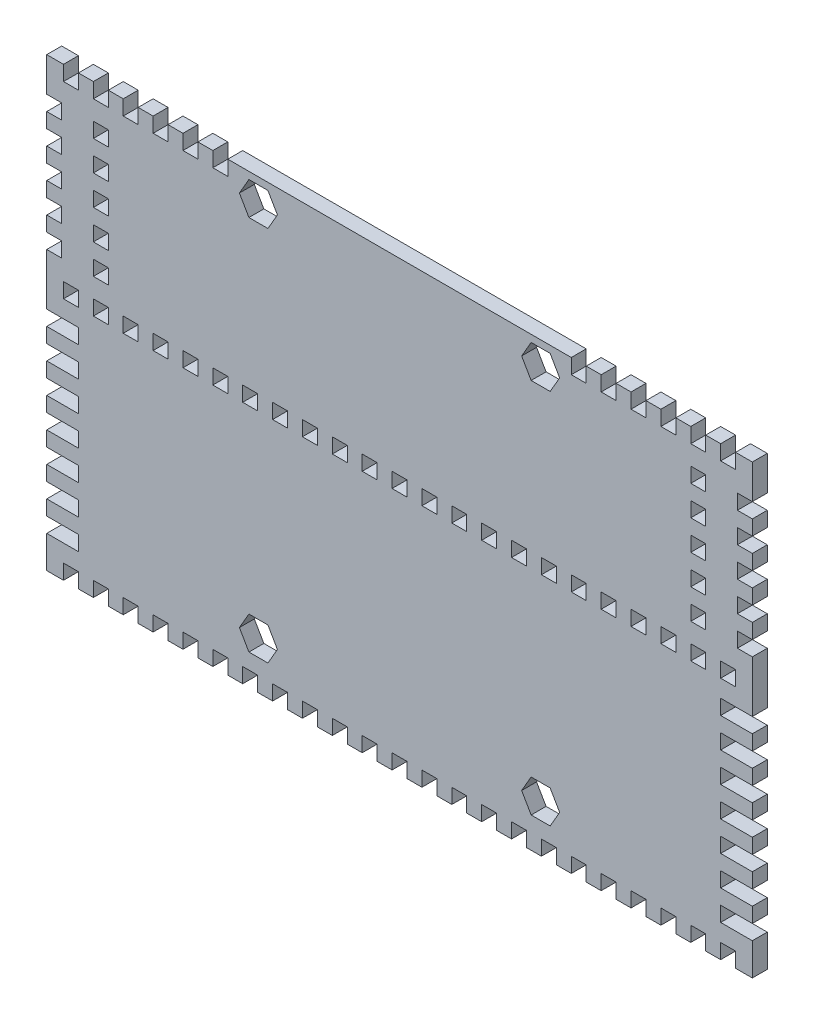
SolidWorks part; units mm, degrees
ref_plane "Front Plane" through (0, 0, 0) normal (0, 0, 1) x (1, 0, 0)
ref_plane "Top Plane" through (0, 0, 0) normal (0, 1, 0) x (1, 0, 0)
ref_plane "Right Plane" through (0, 0, 0) normal (1, 0, 0) x (0, 0, -1)
sketch "Sketch1" plane through (0, 0, 0) normal (0, 0, 1) x (1, 0, 0)
  line L1 (75, -27.5) -> (-75, -27.5)
  line L2 (75, -27.5) -> (75, 27.5)
  line L3 (75, 27.5) -> (-75, 27.5)
  line L4 (-75, -27.5) -> (-75, 27.5)
  line L5 (75, -27.5) -> (-75, 27.5) construction
  line L6 (75, 27.5) -> (-75, -27.5) construction
  point P0 (0, 0)
  dimension "D1" = 150
  dimension "D2" = 55
extrude "Boss-Extrude1" add sketch "Sketch1" along normal blind 3.175
sketch "Sketch2" plane through (0, 0, 0) normal (0, 0, -1) x (-1, 0, 0)
  line L0 (-75, 27.5) -> (75, 27.5) construction
  line L1 (-1.5875, 30.675) -> (1.5875, 30.675)
  line L2 (-1.5875, 30.675) -> (-1.5875, 24.325)
  line L3 (-1.5875, 24.325) -> (1.5875, 24.325)
  line L4 (1.5875, 30.675) -> (1.5875, 24.325)
  line L5 (-1.5875, 30.675) -> (1.5875, 24.325) construction
  line L6 (-1.5875, 24.325) -> (1.5875, 30.675) construction
  point P0 (0, 27.5)
  dimension "D1" = 3.175
  dimension "D2" = 6.35
extrude "Cut-Extrude1" cut sketch "Sketch2" against normal up to next
pattern_linear "LPattern1" count 12 spacing 6.35 along (1, 0, 0) count 12 spacing 6.35 along (-1, 0, 0) of "Cut-Extrude1" pattern seed only yes
mirror "Mirror1" about plane through (0, 0, 0) normal (0, 1, 0) of "LPattern1"
sketch "Sketch3" plane through (0, 0, 0) normal (0, 0, -1) x (-1, 0, 0)
  line L0 (-75, -27.5) -> (-75, 27.5) construction
  line L1 (-78.175, 1.5875) -> (-71.825, 1.5875)
  line L2 (-78.175, 1.5875) -> (-78.175, -1.5875)
  line L3 (-78.175, -1.5875) -> (-71.825, -1.5875)
  line L4 (-71.825, 1.5875) -> (-71.825, -1.5875)
  line L5 (-78.175, 1.5875) -> (-71.825, -1.5875) construction
  line L6 (-78.175, -1.5875) -> (-71.825, 1.5875) construction
  point P0 (-75, 0)
  dimension "D1" = 3.175
  dimension "D2" = 6.35
extrude "Cut-Extrude2" cut sketch "Sketch3" against normal blind 10
pattern_linear "LPattern2" count 4 spacing 6.35 along (0, 1, 0) count 4 spacing 6.35 along (0, -1, 0) of "Cut-Extrude2" pattern seed only yes
mirror "Mirror2" about plane through (0, 0, 0) normal (1, 0, 0) of "LPattern2"
sketch "Sketch4" plane through (0, 0, 0) normal (0, 0, -1) x (-1, 0, 0)
  line L0 (-45, 0) -> (-25, 0) construction
  line L1 (-45, 1.5) -> (-25, 1.5)
  line L2 (-45, -1.5) -> (-25, -1.5)
  line L3 (25, 0) -> (45, 0) construction
  line L4 (25, 1.5) -> (45, 1.5)
  line L5 (25, -1.5) -> (45, -1.5)
  arc A0 (-45, 1.5) -> (-45, -1.5) centre (-45, 0) ccw
  arc A1 (-25, -1.5) -> (-25, 1.5) centre (-25, 0) ccw
  arc A2 (25, 1.5) -> (25, -1.5) centre (25, 0) ccw
  arc A3 (45, -1.5) -> (45, 1.5) centre (45, 0) ccw
  point P2 (-35, 0)
  point P9 (35, 0)
  dimension "D1" = 35
  dimension "D2" = 35
  dimension "D3" = 3
  dimension "D4" = 3
  dimension "D5" = 20
  dimension "D6" = 20
extrude "Cut-Extrude3" [suppressed] cut sketch "Sketch4" against normal blind 10
sketch "Sketch5" plane through (0, 0, 0) normal (0, 0, -1) x (-1, 0, 0)
  line L1 (-75, 27.5) -> (75, 27.5)
  line L2 (-75, 27.5) -> (-75, 67.5)
  line L3 (-75, 67.5) -> (75, 67.5)
  line L4 (75, 27.5) -> (75, 67.5)
  dimension "D1" = 40
extrude "Boss-Extrude2" add sketch "Sketch5" against normal up to surface (3.175 mm away) up to face at (0, 0, 3.175)
sketch "Sketch6" plane through (0, 0, 0) normal (0, 0, -1) x (-1, 0, 0)
  line L0 (-35, 44.0688) -> (35, 44.0688) construction
  line L1 (-25, 44.0687) -> (-45, 44.0687) construction
  line L2 (-25, 42.5688) -> (-45, 42.5688)
  line L3 (-25, 45.5688) -> (-45, 45.5688)
  line L4 (25, 44.0687) -> (45, 44.0688) construction
  line L5 (25, 45.5688) -> (45, 45.5688)
  line L6 (25, 42.5687) -> (45, 42.5688)
  arc A0 (-25, 42.5688) -> (-25, 45.5688) centre (-25, 44.0687) ccw
  arc A1 (-45, 45.5688) -> (-45, 42.5688) centre (-45, 44.0687) ccw
  arc A2 (25, 45.5688) -> (25, 42.5687) centre (25, 44.0687) ccw
  arc A3 (45, 42.5688) -> (45, 45.5688) centre (45, 44.0688) ccw
  point P3 (0, 44.0688)
  point P6 (-35, 44.0688)
  point P12 (35, 44.0688)
  dimension "D1" = 70
  dimension "D2" = 3
  dimension "D3" = 3
  dimension "D4" = 20
  dimension "D5" = 20
extrude "Cut-Extrude4" [suppressed] cut sketch "Sketch6" against normal blind 10
sketch "Sketch7" plane through (0, 0, 0) normal (0, 0, -1) x (-1, 0, 0)
  line L0 (75, 67.5) -> (-75, 67.5) construction
  line L1 (0, 67.5) -> (1.5875, 67.5)
  line L3 (0, 64.325) -> (1.5875, 64.325)
  line L4 (1.5875, 67.5) -> (1.5875, 64.325)
  line L6 (0, 64.325) -> (-1.5875, 64.325)
  line L8 (0, 67.5) -> (-1.5875, 67.5)
  line L9 (-1.5875, 64.325) -> (-1.5875, 67.5)
  dimension "D1" = 1.5875
  dimension "D2" = 3.175
  dimension "D3" = 1.5875
extrude "Cut-Extrude5" cut sketch "Sketch7" against normal blind 10
pattern_linear "LPattern3" count 12 spacing 6.35 along (1, 0, 0) count 12 spacing 6.35 along (-1, 0, 0) of "Cut-Extrude5" pattern seed only yes
sketch "Sketch8" plane through (0, 0, 0) normal (0, 0, -1) x (-1, 0, 0)
  line L0 (-68.2625, 24.325) -> (-68.2625, 27.5) construction
  line L1 (-71.825, 20.6375) -> (-68.2625, 20.6375)
  line L2 (-71.825, 20.6375) -> (-71.825, 17.4625)
  line L3 (-71.825, 17.4625) -> (-68.2625, 17.4625)
  line L4 (-68.2625, 20.6375) -> (-68.2625, 17.4625)
extrude "Cut-Extrude6" cut sketch "Sketch8" against normal blind 10
pattern_linear "LPattern4" count 7 spacing 6.35 along (0, -1, 0) of "Cut-Extrude6"
mirror "Mirror3" about plane through (0, 0, 0) normal (1, 0, 0) of "LPattern4"
sketch "Sketch9" plane through (0, 0, 0) normal (0, 0, -1) x (-1, 0, 0)
  line L1 (-30, 62.5) -> (30, 62.5) construction
  line L2 (-30, 62.5) -> (-30, -17.5) construction
  line L3 (-30, -17.5) -> (30, -17.5) construction
  line L4 (30, 62.5) -> (30, -17.5) construction
  line L5 (-30, 62.5) -> (30, -17.5) construction
  line L6 (-30, -17.5) -> (30, 62.5) construction
  line L7 (-39.6875, -27.5) -> (-42.8625, -27.5) construction
  point P0 (0, 22.5)
  dimension "D1" = 60
  dimension "D2" = 80
  dimension "D3" = 50
sketch "Sketch11" plane through (0, 0, 0) normal (0, 0, -1) x (-1, 0, 0)
  line L1 (-36.5125, 67.5) -> (36.5125, 67.5)
  line L2 (-36.5125, 67.5) -> (-36.5125, 64.325)
  line L3 (-36.5125, 64.325) -> (36.5125, 64.325)
  line L4 (36.5125, 67.5) -> (36.5125, 64.325)
extrude "Boss-Extrude3" add sketch "Sketch11" against normal up to surface (3.175 mm away) up to face at (-19.05, 25.9125, 3.175)
sketch "Sketch10" plane through (0, 0, 0) normal (0, 0, -1) x (-1, 0, 0)
  circle A0 centre (-30, 62.5) radius 2.5
  circle A1 centre (30, 62.5) radius 2.5
  circle A2 centre (30, -17.5) radius 2.5
  circle A3 centre (-30, -17.5) radius 2.5
  dimension "D1" = 5
extrude "Cut-Extrude7" cut sketch "Sketch10" against normal blind 10
sketch "Sketch12" plane through (0, 0, 0) normal (0, 0, -1) x (-1, 0, 0)
  line L0 (-75, 67.5) -> (-75, 24.325) construction
  line L1 (-75, 20.6375) -> (-75, 67.5) construction
  line L3 (-78.175, 47.5) -> (-71.825, 47.5)
  line L4 (-78.175, 47.5) -> (-78.175, 44.325)
  line L5 (-78.175, 44.325) -> (-71.825, 44.325)
  line L6 (-71.825, 47.5) -> (-71.825, 44.325)
  line L7 (-78.175, 47.5) -> (-71.825, 44.325) construction
  line L8 (-78.175, 44.325) -> (-71.825, 47.5) construction
  point P5 (-75, 45.9125)
  dimension "D1" = 3.175
  dimension "D2" = 6.35
extrude "Cut-Extrude8" cut sketch "Sketch12" against normal blind 10
pattern_linear "LPattern5" count 3 spacing 6.35 along (0, 1, 0) count 3 spacing 6.35 along (0, -1, 0) of "Cut-Extrude8" pattern seed only yes
mirror "Mirror4" about plane through (0, 0, 0) normal (1, 0, 0) of "LPattern5"
sketch "Sketch13" plane through (0, 0, 0) normal (0, 0, -1) x (-1, 0, 0)
  line L1 (-65.0875, 47.5) -> (-61.9125, 47.5)
  line L2 (-65.0875, 47.5) -> (-65.0875, 44.325)
  line L3 (-65.0875, 44.325) -> (-61.9125, 44.325)
  line L4 (-61.9125, 47.5) -> (-61.9125, 44.325)
extrude "Cut-Extrude9" cut sketch "Sketch13" against normal blind 10
pattern_linear "LPattern6" count 3 spacing 6.35 along (0, 1, 0) count 3 spacing 6.35 along (0, -1, 0) of "Cut-Extrude9" pattern seed only yes
mirror "Mirror5" about plane through (0, 0, 0) normal (1, 0, 0) of "LPattern6"
sketch "Sketch14" plane through (0, 0, 0) normal (0, 0, -1) x (-1, 0, 0)
  line L1 (-25.9585, 62.5) -> (-27.9793, 66)
  line L2 (-27.9793, 66) -> (-32.0207, 66)
  line L3 (-32.0207, 66) -> (-34.0415, 62.5)
  line L4 (-34.0415, 62.5) -> (-32.0207, 59)
  line L5 (-32.0207, 59) -> (-27.9793, 59)
  line L6 (-27.9793, 59) -> (-25.9585, 62.5)
  line L7 (25.9585, 62.5) -> (27.9793, 59)
  line L8 (27.9793, 59) -> (32.0207, 59)
  line L9 (32.0207, 59) -> (34.0415, 62.5)
  line L10 (34.0415, 62.5) -> (32.0207, 66)
  line L11 (32.0207, 66) -> (27.9793, 66)
  line L12 (27.9793, 66) -> (25.9585, 62.5)
  line L13 (25.9585, -17.5) -> (27.9793, -21)
  line L14 (27.9793, -21) -> (32.0207, -21)
  line L15 (32.0207, -21) -> (34.0415, -17.5)
  line L16 (34.0415, -17.5) -> (32.0207, -14)
  line L17 (32.0207, -14) -> (27.9793, -14)
  line L18 (27.9793, -14) -> (25.9585, -17.5)
  line L19 (-25.9585, -17.5) -> (-27.9793, -14)
  line L20 (-27.9793, -14) -> (-32.0207, -14)
  line L21 (-32.0207, -14) -> (-34.0415, -17.5)
  line L22 (-34.0415, -17.5) -> (-32.0207, -21)
  line L23 (-32.0207, -21) -> (-27.9793, -21)
  line L24 (-27.9793, -21) -> (-25.9585, -17.5)
  circle A0 centre (-30, 62.5) radius 3.5 construction
  circle A1 centre (30, 62.5) radius 3.5 construction
  circle A2 centre (30, -17.5) radius 3.5 construction
  circle A3 centre (-30, -17.5) radius 3.5 construction
  dimension "D1" = 7
  dimension "D2" = 7
  dimension "D3" = 7
  dimension "D4" = 7
extrude "Cut-Extrude10" cut sketch "Sketch14" against normal blind 10
